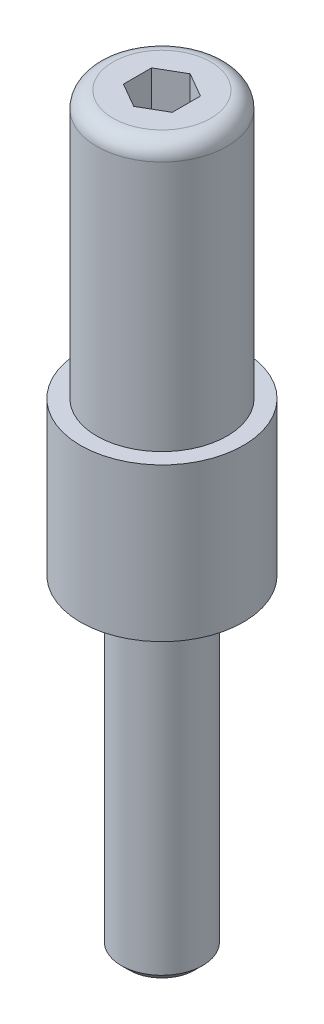
SolidWorks part; units mm, degrees
ref_plane "前视基准面" through (0, 0, 0) normal (0, 0, 1) x (1, 0, 0)
ref_plane "上视基准面" through (0, 0, 0) normal (0, 1, 0) x (1, 0, 0)
ref_plane "右视基准面" through (0, 0, 0) normal (1, 0, 0) x (0, 0, -1)
sketch "草图1" plane through (0, 0, 0) normal (0, 0, 1) x (1, 0, 0)
  line L0 (0, 25.8) -> (3, 25.8)
  line L1 (4, 24.8) -> (4, 9.4)
  line L2 (4, 9.4) -> (5, 9.4)
  line L3 (5, 9.4) -> (5, 0)
  line L4 (5, 0) -> (2.5, 0)
  line L5 (2.5, 0) -> (2.5, -19.5095)
  line L6 (2.5, -19.5095) -> (2.0095, -20)
  line L7 (2.0095, -20) -> (0, -20)
  line L8 (0, -20) -> (0, 25.8)
  line L9 (0, -20) -> (0, 25.8) construction
  arc A0 (3, 25.8) -> (4, 24.8) centre (3, 24.8) cw
revolve "旋转1" add sketch "草图1" angle 360 about L9 reverse direction yes
cosmetic thread "装饰螺纹线1" parameters "D1"=19.2, "D2"=4.019
ref_plane "基准面4" through (0, 25.8, 0) normal (0, 1, 0) x (1, 0, 0)
sketch "草图2" plane through (0, 25.8, 0) normal (0, 1, 0) x (1, 0, 0)
  line L0 (-1.5, 0.866) -> (-1.5, -0.866)
  line L1 (-1.5, -0.866) -> (0, -1.7321)
  line L2 (0, -1.7321) -> (1.5, -0.866)
  line L3 (1.5, -0.866) -> (1.5, 0.866)
  line L4 (1.5, 0.866) -> (0, 1.7321)
  line L5 (0, 1.7321) -> (-1.5, 0.866)
extrude "切除-拉伸1" cut sketch "草图2" along normal blind 3 and the other way blind 3
ref_plane "A XY" through (0, 0, 0) normal (0, 1, 0) x (1, 0, 0)
ref_plane "A XZ" through (0, 0, 0) normal (0, 0, 1) x (1, 0, 0)
ref_plane "A YZ" through (0, 0, 0) normal (1, 0, 0) x (0, 0, -1)
ref_axis "A X" through (-80.9, 0, 0) along (1, 0, 0)
ref_axis "A Y" through (0, 0, 50) along (0, 0, -1)
ref_axis "A Z" through (0, 50, 0) along (0, -1, 0)
sketch3d "A"
  point P0 (0, 0, 0)
